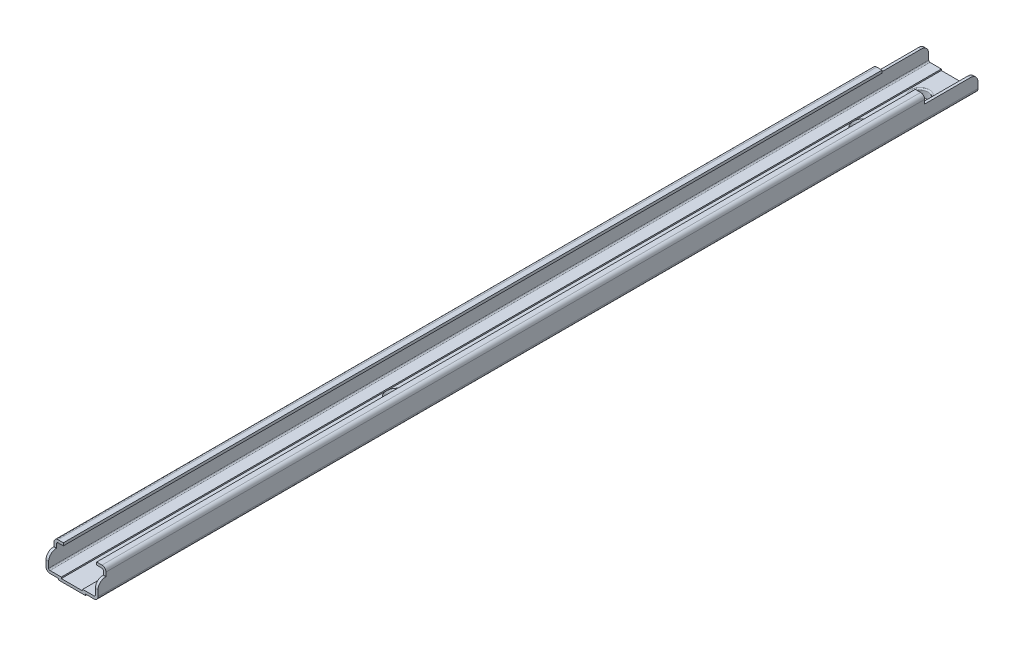
SolidWorks part; units mm, degrees
note: '?' marks a value the reader was unsure of.
ref_plane "Face" through (0, 0, 0) normal (0, 0, 1) x (1, 0, 0)
ref_plane "Dessus" through (0, 0, 0) normal (0, 1, 0) x (1, 0, 0)
ref_plane "Droite" through (0, 0, 0) normal (1, 0, 0) x (0, 0, -1)
sketch "Esquisse1" plane through (0, 0, 0) normal (0, 0, 1) x (1, 0, 0)
  line L0 (-5, 0) -> (5, 0)
  line L1 (9.75, 0.5) -> (9.75, 10)
  line L2 (9.75, 10) -> (6.25, 10)
  line L3 (9.75, 0.5) -> (5, 0.5)
  line L4 (5, 0) -> (5, 0.5)
  line L5 (0, 0) -> (0, 10.7996) construction
  line L6 (-5, 0) -> (-5, 0.5)
  line L7 (-9.75, 0.5) -> (-5, 0.5)
  line L8 (-9.75, 10) -> (-6.25, 10)
  line L9 (-9.75, 0.5) -> (-9.75, 10)
  point P9 (9.75, 0.5)
  point P12 (9.75, 10)
  dimension "D2" = 5
  dimension "D1" = 9.75
  dimension "D3" = 3.5
  dimension "D4" = 0.5
  dimension "D5" = 10
extrude "Base-Extru.-Mince" add sketch "Esquisse1" along normal blind 330 thin
fillet "Congé1" radius 1.5
fillet "Congé2" radius 0.5
sketch "Esquisse2" plane through (0, 0, 0) normal (1, 0, 0) x (0, 0, -1)
  line L0 (-330, 0) -> (-330, 4.2)
  line L1 (-330, 8.5) -> (-330, 2) construction
  line L2 (-327.2, 7) -> (-327, 7)
  line L3 (-327, 7) -> (-327, 10)
  line L4 (0, 10) -> (-330, 10) construction
  line L5 (-330, 0) -> (-332.4288, 0)
  line L6 (-332.4288, 0) -> (-332.4288, 10)
  line L7 (-332.4288, 10) -> (-327, 10)
  line L10 (0.9198, 11.1637) -> (-20, 11.1637)
  line L11 (0.9198, 0) -> (0.9198, 11.1637)
  line L12 (0, 0) -> (0.9198, 0)
  line L13 (-20, 7) -> (-20, 11.1637)
  line L14 (-2.8, 7) -> (-20, 7)
  line L15 (0, 0) -> (0, 4.2)
  arc A0 (-330, 4.2) -> (-327.2, 7) centre (-327.2, 4.2) cw
  arc A1 (0, 4.2) -> (-2.8, 7) centre (-2.8, 4.2) ccw
  point P13 (-330, 7)
  dimension "D3" = 2.8
  dimension "D1" = 7
  dimension "D2" = 3
  dimension "D5" = 20
extrude "Enlèv. mat.-Extru.1" cut sketch "Esquisse2" against normal through all and the other way through all
sketch "Esquisse3" plane through (0, 0, 0) normal (0, 1, 0) x (1, 0, 0)
  line L0 (0, 0) -> (0, -334.7531) construction
  circle A0 centre (0, -12) radius 3
  dimension "D1" = 6
  dimension "D2" = 12
extrude "Enlèv. mat.-Extru.4" cut sketch "Esquisse3" along normal blind 3
sketch "Esquisse4" plane through (0, 0, 0) normal (0, -1, 0) x (1, 0, 0)
  circle A0 centre (0, 12) radius 3 construction
  circle A1 centre (0, 12) radius 3
  circle A2 centre (0, 12) radius 3.5
  dimension "D1" = 0.5
extrude "Boss.-Extru.1" add sketch "Esquisse4" along normal blind 2
fillet "Congé3" radius 0.5
sketch "Esquisse5" plane through (0, 1, 0) normal (0, 1, 0) x (-1, 0, 0)
  circle A0 centre (0, 208) radius 4.25
  circle A1 centre (0, 12) radius 3 construction
  circle A3 centre (0, 34) radius 4.25
  dimension "D1" = 8.5
  dimension "D2" = 8.5
  dimension "D3" = 22
extrude "Boss.-Extru.2" add sketch "Esquisse5" against normal blind 1.5 draft 45
sketch "Esquisse6" plane through (0, 1, 0) normal (0, 1, 0) x (-1, 0, 0)
  circle A1 centre (0, 33) radius 4
  circle A3 centre (0, 208) radius 4
  dimension "D1" = 8
  dimension "D2" = 8
extrude "Enlèv. mat.-Extru.6" cut sketch "Esquisse6" against normal blind 2 draft 45
ref_axis "Axe1" through (0, 0.5, 12) along (0, -1, 0)?
ref_axis "Axe2" through (0, 1, 33) along (0, 0, -1)?
